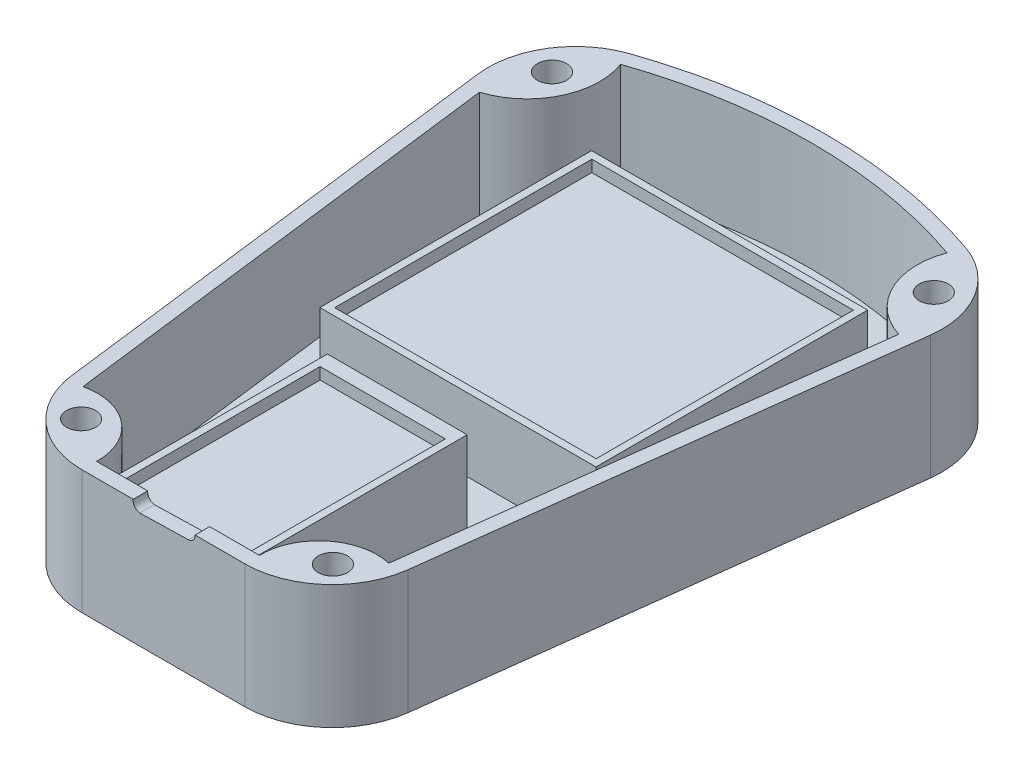
SolidWorks part; units mm, degrees
ref_plane "Front Plane" through (0, 0, 0) normal (0, 0, 1) x (1, 0, 0)
ref_plane "Top Plane" through (0, 0, 0) normal (0, 1, 0) x (1, 0, 0)
ref_plane "Right Plane" through (0, 0, 0) normal (1, 0, 0) x (0, 0, -1)
sketch "Sketch2" plane through (0, 0, 0) normal (0, 1, 0) x (1, 0, 0)
  line L0 (0, -78.985) -> (0, 71.015) construction
  line L1 (-71.9346, 0) -> (78.0654, 0) construction
  line L2 (0, 51.3965) -> (-30, 51.3965) construction
  line L3 (0, 51.3965) -> (30, 51.3965) construction
  line L4 (30, 51.3965) -> (30, -28.6035) construction
  line L5 (0, -28.6035) -> (11.1722, -28.6035) construction
  line L6 (0, -28.6035) -> (-11.1722, -28.6035) construction
  line L7 (-29.0575, 43.8564) -> (-21.095, -19.8439)
  line L8 (29.0575, 43.8564) -> (21.095, -19.8439)
  line L9 (-11.1722, -28.6035) -> (11.1722, -28.6035)
  arc A0 (11.1722, -28.6035) -> (21.095, -19.8439) centre (11.1722, -18.6035) ccw
  arc A1 (-11.1722, -28.6035) -> (-21.095, -19.8439) centre (-11.1722, -18.6035) cw
  arc A2 (-22.405, 54.5469) -> (22.405, 54.5469) centre (0, -10.1976) cw
  arc A3 (29.0575, 43.8564) -> (22.405, 54.5469) centre (19.1347, 45.0967) ccw
  arc A4 (-22.405, 54.5469) -> (-29.0575, 43.8564) centre (-19.1347, 45.0967) ccw
  point P16 (0, -33.0041)
  point P18 (20, -28.6035)
  point P21 (-20, -28.6035)
  dimension "D8" = 10
  dimension "D9" = 10
  dimension "D1" = 150
  dimension "D2" = 150
  dimension "D3" = 30
  dimension "D4" = 30
  dimension "D5" = 80
  dimension "D6" = 20
  dimension "D7" = 20
extrude "Boss-Extrude1" add sketch "Sketch2" along normal blind 15 contours A2 A3 L8 A0 L9 A1 L7 A4
shell "Shell1" thickness 2 removed face at (0, 15, -12.7853) outward yes
sketch "Sketch3" plane through (0, 0, 0) normal (0, 1, 0) x (1, 0, 0)
  line L0 (-29.0575, 43.8564) -> (-21.095, -19.8439) construction
  line L1 (0, -9.35) -> (0, 9.35) construction
  arc A0 (-28.7693, 41.5508) -> (-22.405, 54.5469) centre (-31.7865, 51.0847) ccw
  arc A1 (-22.405, 54.5469) -> (-29.0575, 43.8564) centre (-19.1347, 45.0967) ccw construction
  arc A2 (-22.405, 54.5469) -> (-29.0575, 43.8564) centre (-19.1347, 45.0967) ccw construction
  arc A3 (-20.9604, -20.6507) -> (-11.1722, -28.6035) centre (-19.1707, -28.448) cw
  arc A4 (-21.095, -19.8439) -> (-11.1722, -28.6035) centre (-11.1722, -18.6035) ccw construction
  arc A5 (-22.405, 54.5469) -> (-28.7693, 41.5508) centre (-19.0891, 44.8666) ccw
  arc A6 (-20.9604, -20.6507) -> (-11.1722, -28.6035) centre (-11.1722, -18.6035) ccw
  arc A7 (20.9604, -20.6507) -> (11.1722, -28.6035) centre (11.1722, -18.6035) cw
  arc A8 (20.9604, -20.6507) -> (11.1722, -28.6035) centre (19.1707, -28.448) ccw
  arc A9 (22.405, 54.5469) -> (28.7693, 41.5508) centre (19.0891, 44.8666) cw
  arc A10 (28.7693, 41.5508) -> (22.405, 54.5469) centre (31.7865, 51.0847) cw
  arc M7 (-21.095, -19.8439) -> (-11.1722, -28.6035) centre (-11.1722, -18.6035) ccw
  line M10 (21.095, -19.8439) -> (29.0575, 43.8564)
  arc M11 (29.0575, 43.8564) -> (22.405, 54.5469) centre (19.1347, 45.0967) ccw
  dimension "D1" = 10
  dimension "D2" = 8
extrude "Boss-Extrude2" add sketch "Sketch3" along normal blind 15 contours A10 M10 M11 | A3 M7 | A5 A0 | A8 A7 region at (-15.8421, 0, 24.3513) region at (25.472, 0, -48.0703)
sketch "Sketch4" plane through (0, 15, 0) normal (0, 1, 0) x (1, 0, 0)
  line L0 (0, -9.35) -> (0, 9.35) construction
  circle A0 centre (-26.2038, 48.9328) radius 2
  arc A1 (-23.059, 56.4369) -> (-31.042, 43.6083) centre (-19.1347, 45.0967) ccw construction
  arc A2 (-28.7693, 41.5508) -> (-22.405, 54.5469) centre (-31.7865, 51.0847) ccw construction
  circle A3 centre (-17.2797, -24.6188) radius 2
  arc A4 (-23.0795, -20.092) -> (-11.1722, -30.6035) centre (-11.1722, -18.6035) ccw construction
  circle A5 centre (17.2797, -24.6188) radius 2
  circle A6 centre (26.2038, 48.9328) radius 2
  point P5 (-29.3231, 51.4368)
  point P10 (-22.8056, 46.6867)
  point P15 (-19.1138, -27.5997)
  dimension "D1" = 4
  dimension "D4" = 4
  dimension "D2" = 4
  dimension "D3" = 4.0735
  dimension "D5" = 3.5
extrude "Cut-Extrude3" cut sketch "Sketch4" against normal up to surface (17 mm away) contours A3 | A0 | A6 | A5 up to face at (0, -2, -12.6126)
sketch "Sketch5" plane through (-2.134, 0, 0) normal (0, 1, 0) x (1, 0, 0)
  line L1 (-17, 47.3) -> (20.9, 47.3)
  line L2 (-17, 47.3) -> (-17, 10)
  line L3 (-17, 10) -> (20.9, 10)
  line L4 (20.9, 47.3) -> (20.9, 10)
  dimension "D1" = 37.9
  dimension "D2" = 37.3
extrude "Boss-Extrude3" add sketch "Sketch5" along normal blind 10
sketch "Sketch7" plane through (-2.134, 10, 0) normal (0, 1, 0) x (1, 0, 0)
sketch "Sketch8" plane through (48.8983, 10, 0) normal (0, 1, 0) x (1, 0, 0)
  line L1 (-67, 46.3) -> (-31.1, 46.3)
  line L2 (-67, 46.3) -> (-67, 11)
  line L3 (-67, 11) -> (-31.1, 11)
  line L4 (-31.1, 46.3) -> (-31.1, 11)
extrude "Cut-Extrude4" cut sketch "Sketch8" against normal blind 1.6
sketch "Sketch9" plane through (0, 0, 0) normal (0, 1, 0) x (1, 0, 0)
  line L0 (-11.1722, -28.6035) -> (11.1722, -28.6035) construction
  line L1 (-9.5, -28.6035) -> (9.7, -28.6035)
  line L2 (-9.5, -28.6035) -> (-9.5, 1.3965)
  line L3 (-9.5, 1.3965) -> (9.7, 1.3965)
  line L4 (9.7, -28.6035) -> (9.7, 1.3965)
  line L5 (0, -9.35) -> (0, 9.35) construction
  dimension "D1" = 19.2
  dimension "D2" = 9.5
  dimension "D3" = 30
extrude "Boss-Extrude5" add sketch "Sketch9" along normal blind 13.6 contours L2 L1 L4 L3
sketch "Sketch11" plane through (0, 13.6, 0) normal (0, 1, 0) x (1, 0, 0)
  line L0 (-9.5, -28.6035) -> (9.7, -28.6035) construction
  line L1 (-8.5, -28.6035) -> (8.7, -28.6035)
  line L2 (-8.5, -28.6035) -> (-8.5, -0.6035)
  line L3 (-8.5, -0.6035) -> (8.7, -0.6035)
  line L4 (8.7, -28.6035) -> (8.7, -0.6035)
  line L5 (-9.5, -28.6035) -> (-9.5, 1.3965) construction
  line L6 (9.7, -28.6035) -> (9.7, 1.3965) construction
  dimension "D1" = 28
  dimension "D2" = 1
  dimension "D3" = 1
extrude "Cut-Extrude7" cut sketch "Sketch11" against normal blind 1.6
sketch "Sketch12" plane through (0, 0, 30.6035) normal (0, 0, 1) x (1, 0, 0)
  line L0 (-4.15, 15) -> (4.35, 15)
  line L1 (-11.1722, 15) -> (11.1722, 15) construction
  line L2 (-3.25, 13.8219) -> (3.45, 13.9857)
  arc A0 (-4.15, 15) -> (-3.25, 13.8219) centre (-3.111, 14.861) ccw
  arc A1 (3.45, 13.9857) -> (4.35, 15) centre (3.3928, 14.9428) ccw
  dimension "D1" = 8.5
  dimension "D2" = 4.35
  dimension "D3" = 1.4
  dimension "D4" = 6.7
  dimension "D5" = 0.9
extrude "Cut-Extrude8" cut sketch "Sketch12" against normal up to surface (2 mm away) up to face at (0.0667, 9.0333, 28.6035)
